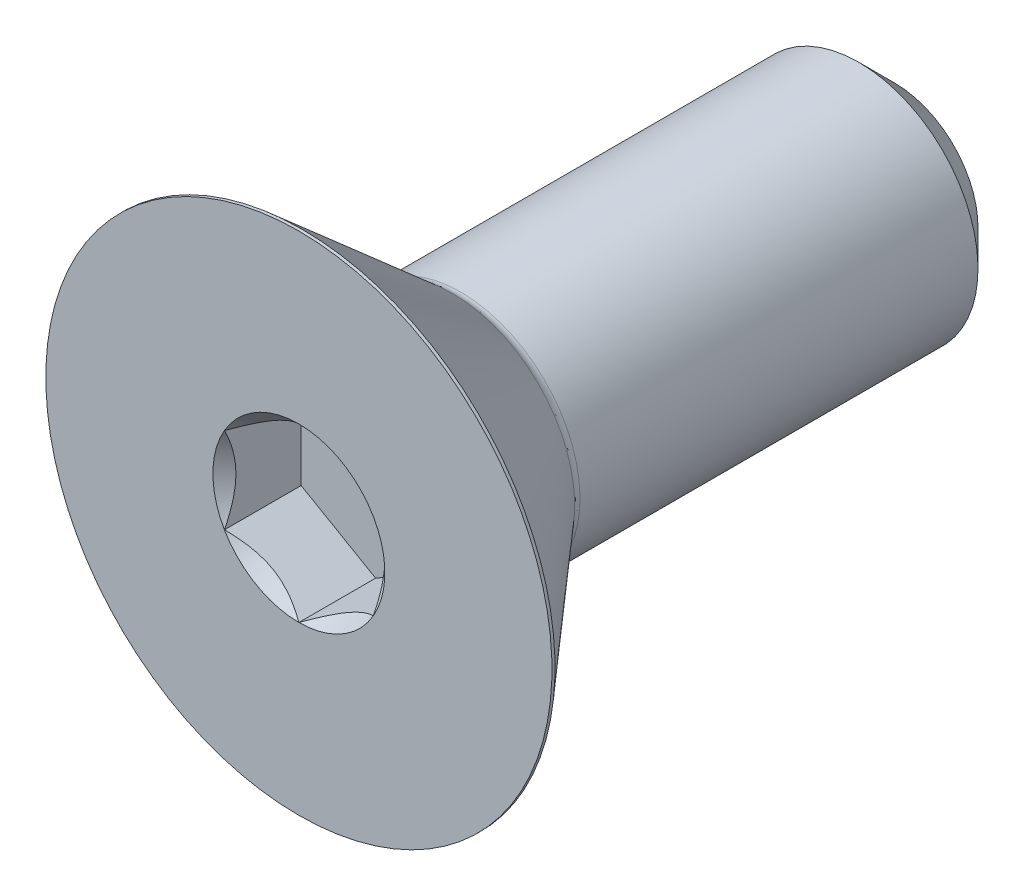
SolidWorks part; units mm, degrees
material "Cast Alloy Steel"
ref_plane "Front Plane" through (0, 0, 0) normal (0, 0, 1) x (1, 0, 0)
ref_plane "Top Plane" through (0, 0, 0) normal (0, 1, 0) x (1, 0, 0)
ref_plane "Right Plane" through (0, 0, 0) normal (1, 0, 0) x (0, 0, -1)
sketch "Sketch1" plane through (0, 0, 0) normal (1, 0, 0) x (0, 0, -1)
  line L0 (-7.9375, 0) -> (7.9375, 0) construction
  line L1 (-7.9375, 0) -> (-7.9375, 6.7437)
  line L2 (-7.9375, 6.7437) -> (-7.8557, 6.7437)
  line L3 (-7.8557, 6.7437) -> (-3.8481, 3.2599)
  line L4 (-7.8557, -6.7437) -> (-3.8481, -3.2599)
  line L5 (7.9375, 0) -> (7.9375, 3.175)
  line L6 (7.9375, 3.175) -> (-3.8481, 3.175)
  line L7 (6.985, 3.175) -> (7.9375, 2.2225)
  line L8 (7.8581, 3.3125) -> (8.4931, 2.2126) construction
  line L9 (8.4931, 2.2126) -> (9.1281, 3.3125) construction
  line L10 (9.1281, 3.3125) -> (7.8581, 3.3125) construction
  line L11 (7.8978, 3.2437) -> (9.0884, 3.2437)
  line L12 (9.0884, 3.2437) -> (8.5725, 2.3501)
  line L13 (8.5725, 2.3501) -> (8.4138, 2.3501)
  line L14 (8.4138, 2.3501) -> (7.8978, 3.2437)
  line L15 (8.4931, 2.3501) -> (8.4931, 2.2126) construction
  line L16 (7.9375, 3.175) -> (9.0488, 3.175) construction
  line L17 (8.4931, 3.3125) -> (8.4931, 3.175) construction
  line L18 (7.9375, -3.175) -> (-3.8481, -3.175)
  arc A0 (-3.8481, 3.2599) -> (-3.6209, 3.175) centre (-3.6209, 3.5213) ccw
  point P2 (0, 0)
  point P23 (-5.8928, 0)
  point P27 (8.4931, 3.2437)
  point P30 (6.0325, -3.175)
  point P34 (-7.8557, -6.7437)
  dimension "Length" = 15.875
  dimension "Head Height" = 4.0894
  dimension "Head Diameter" = 13.4874
  dimension "Countersink Angle" = 82
  dimension "Thread Diameter" = 6.35
  dimension "D2" = 0.0818
  dimension "Pitch" = 1.27
  dimension "D4" = 0.1588
  dimension "D3" = 45
  dimension "D5" = 0.9525
  dimension "D6" = 2.0447
  dimension "D1" = 1.905
sketch "Sketch2" plane through (0, 0, 0) normal (0, 0, 1) x (1, 0, 0)
  line L1 (0, 2.2914) -> (-1.9844, 1.1457)
  line L2 (-1.9844, 1.1457) -> (-1.9844, -1.1457)
  line L3 (-1.9844, -1.1457) -> (0, -2.2914)
  line L4 (0, -2.2914) -> (1.9844, -1.1457)
  line L5 (1.9844, -1.1457) -> (1.9844, 1.1457)
  line L6 (1.9844, 1.1457) -> (0, 2.2914)
  circle A0 centre (0, 0) radius 1.9844 construction
  dimension "Drive Size" = 3.9688
sketch "Sketch11" plane through (0, 0, 0) normal (1, 0, 0) x (0, 0, -1)
  line L0 (-7.8557, 6.7437) -> (-3.8481, 3.2599) construction
  line L1 (-7.9375, 0) -> (-7.9375, 6.7437) construction
  line L2 (-7.8557, 6.7437) -> (-3.8481, 3.2599)
  line L3 (-7.9375, 0) -> (-7.9375, 6.7437)
  line L4 (-7.9375, 6.7437) -> (-7.8557, 6.7437) construction
  line L5 (-7.9375, 6.7437) -> (-7.8557, 6.7437)
  line L6 (-3.6209, 3.175) -> (6.985, 3.175)
  line L7 (6.985, 3.175) -> (7.9375, 2.2225)
  line L8 (7.9375, 2.2225) -> (7.9375, 0)
  line L9 (7.9375, 0) -> (-7.9375, 0)
  arc A0 (-3.8481, 3.2599) -> (-3.6209, 3.175) centre (-3.6209, 3.5213) ccw construction
  arc A1 (-3.8481, 3.2599) -> (-3.6209, 3.175) centre (-3.6209, 3.5213) ccw
revolve "Revolve1" add sketch "Sketch11" angle 360 about L9
sketch "Sketch9" plane through (0, 0, 7.9375) normal (0, 0, 1) x (1, 0, 0)
  line L0 (1.9844, -1.1457) -> (1.9844, 1.1457) construction
  line L1 (0, -2.2914) -> (1.9844, -1.1457) construction
  line L2 (-1.9844, -1.1457) -> (0, -2.2914) construction
  line L3 (-1.9844, 1.1457) -> (-1.9844, -1.1457) construction
  line L4 (0, 2.2914) -> (-1.9844, 1.1457) construction
  line L5 (1.9844, 1.1457) -> (0, 2.2914) construction
  line L6 (1.9844, -1.1457) -> (1.9844, 1.1457)
  line L7 (0, -2.2914) -> (1.9844, -1.1457)
  line L8 (-1.9844, -1.1457) -> (0, -2.2914)
  line L9 (-1.9844, 1.1457) -> (-1.9844, -1.1457)
  line L10 (0, 2.2914) -> (-1.9844, 1.1457)
  line L11 (1.9844, 1.1457) -> (0, 2.2914)
sketch "Sketch10" plane through (0, 0, 7.9375) normal (0, 0, 1) x (1, 0, 0)
  circle A0 centre (0, 0) radius 2.2914
extrude "Cut-Extrude2" cut sketch "Sketch10" against normal up to vertex (2.0447 mm away) draft 45 up to point (0, 0, 5.8928)
extrude "Cut-Extrude1" cut sketch "Sketch9" against normal up to vertex (2.0447 mm away) up to point (0, 0, 5.8928)
ref_plane "Plane1" [suppressed] through (0, 0, 3.6209) normal (0, 0, 1) x (1, 0, 0)
split "Split1" [suppressed] bodies to split 111
sketch "Sketch3" [suppressed] plane through (0, 0, -7.9375) normal (0, 0, -1) x (-1, 0, 0)
  circle A0 centre (0, 0) radius 3.175 construction
  circle A1 centre (0, 0) radius 3.175
curve "Helix/Spiral1" [suppressed] pitch 1.27 height 15.875 turns 12.5
sketch "Sketch4" [suppressed] plane through (0, 0, 0) normal (1, 0, 0) x (0, 0, -1)
  line L0 (7.8978, 3.2437) -> (9.0884, 3.2437) construction
  line L1 (8.4137, 2.3501) -> (7.8978, 3.2437) construction
  line L2 (8.5725, 2.3501) -> (8.4137, 2.3501) construction
  line L3 (9.0884, 3.2437) -> (8.5725, 2.3501) construction
  line L4 (7.8978, 3.2437) -> (9.0884, 3.2437)
  line L5 (8.4137, 2.3501) -> (7.8978, 3.2437)
  line L6 (8.5725, 2.3501) -> (8.4137, 2.3501)
  line L7 (9.0884, 3.2437) -> (8.5725, 2.3501)
sweep "Cut-Sweep1" [suppressed] cut profiles "Sketch4" path "Helix/Spiral1"
sketch "Sketch7" [suppressed] plane through (0, 0, 3.6209) normal (0, 0, 1) x (1, 0, 0)
  circle A0 centre (0, 0) radius 3.175
extrude "Boss-Extrude2" [suppressed] add sketch "Sketch7" against normal up to next draft 20
ref_axis "Axis1" through (0, 0, 3.6209) along (0, 0, -1)
sketch "Sketch12" [suppressed] plane through (0, 0, 0) normal (1, 0, 0) x (0, 0, -1)
  line L0 (-5.8928, 2.2914) -> (-7.9375, 2.2914) construction
  line L1 (-5.8928, 2.2914) -> (-7.9375, 2.2914)
  line L2 (-5.8928, 2.2914) -> (-5.8928, 0)
  line L3 (-5.8928, 0) -> (-114.3, 0)
  line L4 (-114.3, 0) -> (-114.3, 23.8242)
  line L5 (-114.3, 23.8242) -> (-110.3312, 23.8242)
  line L6 (-110.3312, 23.8242) -> (-110.3312, 2.2914)
  line L7 (-110.3312, 2.2914) -> (-31.3944, 2.2914)
  line L8 (-31.3944, 2.2914) -> (-31.3944, 106.7298)
  line L9 (-31.3944, 106.7298) -> (-27.4256, 106.7298)
  line L10 (-27.4256, 106.7298) -> (-27.4256, 2.2914)
  line L11 (-27.4256, 2.2914) -> (-7.9375, 2.2914)
  dimension "D1" = 108.4072
  dimension "D2" = 3.9688
  dimension "D3" = 21.5328
  dimension "D4" = 25.5016
  dimension "D5" = 104.4384
revolve "Revolve2" [suppressed] add sketch "Sketch12" angle 360 about axis through (0, 0, 3.6209) along (0, 0, -1)
equation "\"D2@Sketch1\"=\"Head Height@Sketch1\"/50"
equation "\"D4@Sketch1\" = \"Pitch@Sketch1\" / 8"
equation "\"D5@Sketch1\"=\"Pitch@Sketch1\"*0.75"
equation "\"D4@Helix/Spiral1\"=\"Pitch@Sketch1\""
equation "\"D3@Helix/Spiral1\"=\"Length@Sketch1\""
equation "\"D6@Sketch1\"=\"Head Height@Sketch1\"/2"
equation "\"D1@Sketch1\"=\"Pitch@Sketch1\"*1.5"
